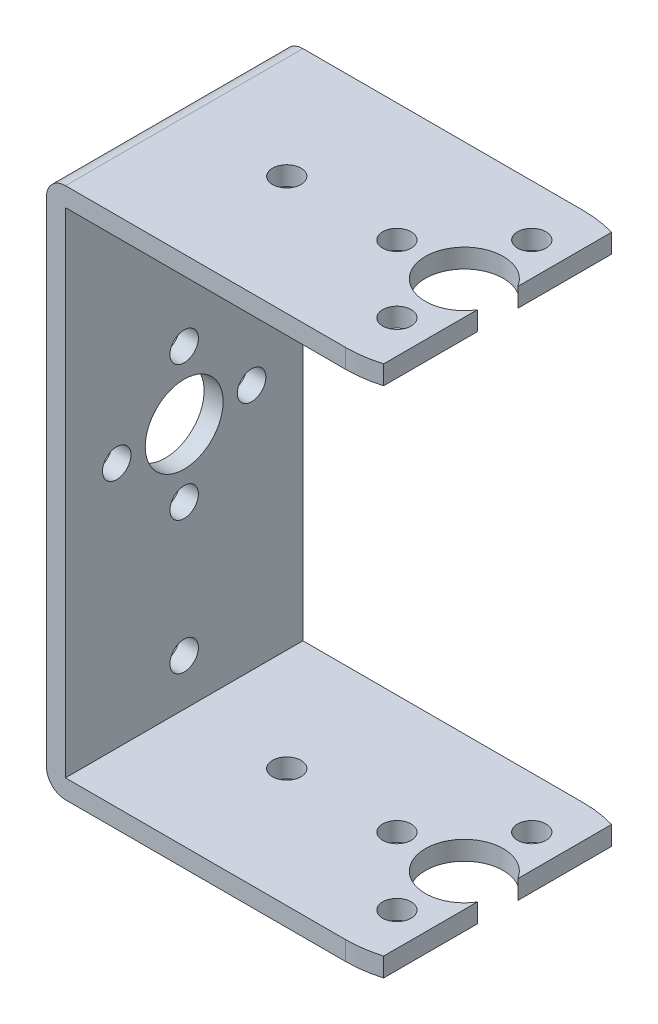
SolidWorks part; units mm, degrees
ref_plane "前视基准面" through (0, 0, 0) normal (0, 0, 1) x (1, 0, 0)
ref_plane "上视基准面" through (0, 0, 0) normal (0, 1, 0) x (1, 0, 0)
ref_plane "右视基准面" through (0, 0, 0) normal (1, 0, 0) x (0, 0, -1)
sketch "草图1" plane through (0, 0, 0) normal (0, 1, 0) x (1, 0, 0)
  line L1 (22, -12.5) -> (-22, -12.5)
  line L2 (22, -12.5) -> (22, 12.5)
  line L3 (22, 12.5) -> (-22, 12.5)
  line L4 (-22, -12.5) -> (-22, 12.5)
  line L5 (22, -12.5) -> (-22, 12.5) construction
  line L6 (22, 12.5) -> (-22, -12.5) construction
  point P0 (0, 0)
  dimension "D1" = 44
  dimension "D2" = 25
extrude "凸台-拉伸1" add sketch "草图1" against normal blind 2
sketch "草图2" plane through (0, 0, 0) normal (0, 1, 0) x (1, 0, 0)
  line L0 (-22, -12.5) -> (22, -12.5) construction
  line L1 (-22, 12.5) -> (-20, 12.5)
  line L2 (-22, 12.5) -> (-22, -12.5)
  line L3 (-22, -12.5) -> (-20, -12.5)
  line L4 (-20, 12.5) -> (-20, -12.5)
  dimension "D1" = 2
extrude "凸台-拉伸2" add sketch "草图2" against normal blind 56
ref_plane "基准面1" through (0, -28, 0) normal (0, 1, 0) x (1, 0, 0)
fillet "圆角1" 2 edges at (22, -1, 12.5) (22, -1, -12.5) type full round first side face at (-6.6667, -19.3333, 12.5) second side face at (-6.6667, -19.3333, -12.5) middle face at (22, -1, 0)
sketch "草图3" plane through (0, 0, 0) normal (0, 1, 0) x (1, 0, 0)
  line L0 (-29.3505, 0) -> (38.6848, 0) construction
  line L1 (9.5, 7.9337) -> (9.5, -10.0875) construction
  circle A0 centre (9.5, 0) radius 4.1
  arc A1 (9.5, -12.5) -> (9.5, 12.5) centre (9.5, 0) ccw construction
  circle A2 centre (2.4, 0) radius 1.5
  circle A3 centre (9.5, 7.1) radius 1.5
  circle A4 centre (16.6, 0) radius 1.5
  circle A5 centre (9.5, -7.1) radius 1.5
  circle A6 centre (-9.2, 0) radius 1.5
  point P21 (9.5, 0)
  dimension "D1" = 8.2
  dimension "D2" = 8.4
  dimension "D3" = 3
  dimension "D4" = 1.5
  dimension "D6" = 3
  dimension "D7" = 8.6
  dimension "D5" = 4
extrude "切除-拉伸2" cut sketch "草图3" against normal up to next
mirror "镜向2" about plane through (0, -28, 0) normal (0, 1, 0) of bodies 110
sketch "草图4" plane through (-22, 0, 0) normal (-1, 0, 0) x (0, 0, 1)
  line L0 (-20.9506, -28) -> (27.7596, -28) construction
  line L1 (-12.5, -56) -> (-12.5, 0) construction
  line L2 (0, 1.1438) -> (0, -59.7626) construction
  circle A0 centre (0, -28) radius 4.1
  circle A1 centre (0, -20.9) radius 1.5
  circle A2 centre (7.1, -28) radius 1.5
  circle A3 centre (0, -35.1) radius 1.5
  circle A4 centre (-7.1, -28) radius 1.5
  circle A5 centre (0, -6.9) radius 1.5
  circle A6 centre (0, -49.1) radius 1.5
  point P4 (-12.5, -28)
  point P21 (0, -28)
  dimension "D1" = 8.2
  dimension "D2" = 3
  dimension "D3" = 1.5
  dimension "D5" = 3
  dimension "D6" = 11
  dimension "D4" = 4
extrude "切除-拉伸3" cut sketch "草图4" against normal up to next
fillet "圆角2" radius 2 2 edges at (-22, -56, 0) (-22, 0, 0)
sketch "草图5" plane through (0, 0, 0) normal (0, 1, 0) x (1, 0, 0)
  line L0 (-22, -12.5) -> (-22, 12.5) construction
  line L1 (13, 15) -> (24, 15)
  line L2 (13, 15) -> (13, -15)
  line L3 (13, -15) -> (24, -15)
  line L4 (24, 15) -> (24, -15)
  point P6 (13, 0)
  dimension "D1" = 11
  dimension "D2" = 30
  dimension "D3" = 35
extrude "切除-拉伸4" cut sketch "草图5" against normal through all
